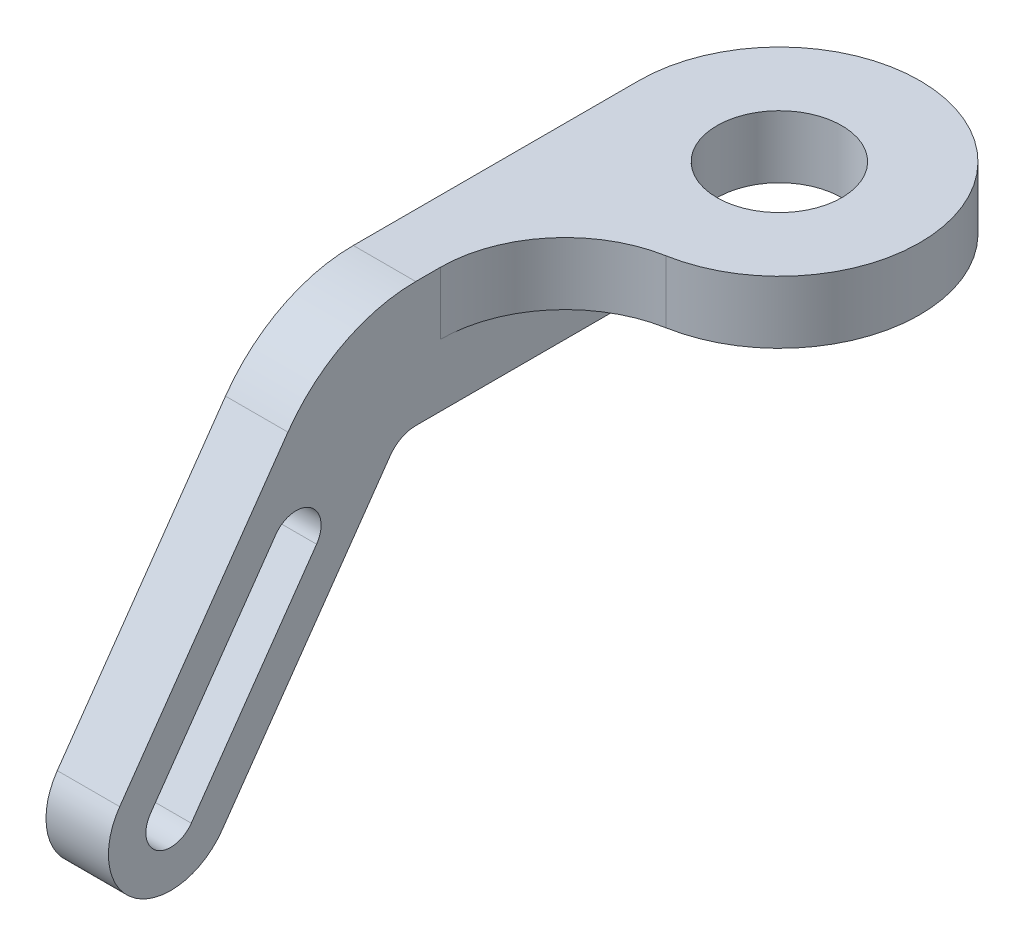
SolidWorks part; units mm, degrees
material "1.0570 (S355J2G3)"
ref_plane "Front Plane" through (0, 0, 0) normal (0, 0, 1) x (1, 0, 0)
ref_plane "Top Plane" through (0, 0, 0) normal (0, 1, 0) x (1, 0, 0)
ref_plane "Right Plane" through (0, 0, 0) normal (1, 0, 0) x (0, 0, -1)
sketch "Sketch1" plane through (0, 0, 0) normal (1, 0, 0) x (0, 0, -1)
  line L0 (0, 0) -> (58.7769, 0)
  line L1 (58.7769, 0) -> (58.7769, -20)
  line L2 (58.7769, -20) -> (10.4113, -20)
  line L3 (10.4113, -20) -> (-18.0315, -60.6207)
  line L4 (-18.0315, -60.6207) -> (-34.4146, -49.1491)
  line L5 (-34.4146, -49.1491) -> (0, 0)
  point P3 (-26.2231, -54.8849)
  dimension "D1" = 20
  dimension "D2" = 125
  dimension "D3" = 60
  dimension "D4" = 85
  dimension "D5" = 20
extrude "Boss-Extrude1" add sketch "Sketch1" along normal blind 10
sketch "Sketch3" plane through (0, 0, 0) normal (-1, 0, 0) x (0, 0, 1)
  line L0 (34.4146, -49.1491) -> (18.0315, -60.6207) construction
  circle A0 centre (26.2231, -54.8849) radius 10
extrude "Boss-Extrude2" add sketch "Sketch3" against normal up to surface (10 mm away) up to face at (10, -24.9616, -12.5865)
sketch "Sketch4" plane through (0, 0, 0) normal (0, 1, 0) x (1, 0, 0)
  line L0 (22.5, 36.2769) -> (10, 36.2769)
  line L1 (10, 58.7769) -> (10, 0) construction
  line L2 (10, 36.2769) -> (10, 40.0686)
  arc A0 (22.5, 36.2769) -> (10, 40.0686) centre (22.5, 58.7769) ccw
  circle A1 centre (22.5, 58.7769) radius 10
  dimension "D1" = 45
  dimension "D2" = 20
extrude "Boss-Extrude3" add sketch "Sketch4" against normal blind 10
fillet "Fillet1" radius 20 1 edges at (10, -5, -36.2769)
fillet "Fillet2" radius 25 1 edges at (5, 0, 0)
fillet "Fillet3" radius 5 1 edges at (5, -20, -10.4113)
sketch "Sketch5" plane through (10, 0, 0) normal (1, 0, 0) x (0, 0, -1)
  line L0 (-26.2231, -54.8849) -> (-6.1479, -26.2146) construction
  line L1 (-29.4997, -52.5906) -> (-9.4245, -23.9203)
  line L2 (-22.9465, -57.1792) -> (-2.8713, -28.5089)
  arc A0 (-29.4997, -52.5906) -> (-22.9465, -57.1792) centre (-26.2231, -54.8849) ccw
  arc A1 (-2.8713, -28.5089) -> (-9.4245, -23.9203) centre (-6.1479, -26.2146) ccw
  point P3 (-16.1855, -40.5497)
  dimension "D1" = 35
  dimension "D2" = 8
extrude "Cut-Extrude1" cut sketch "Sketch5" against normal up to next
